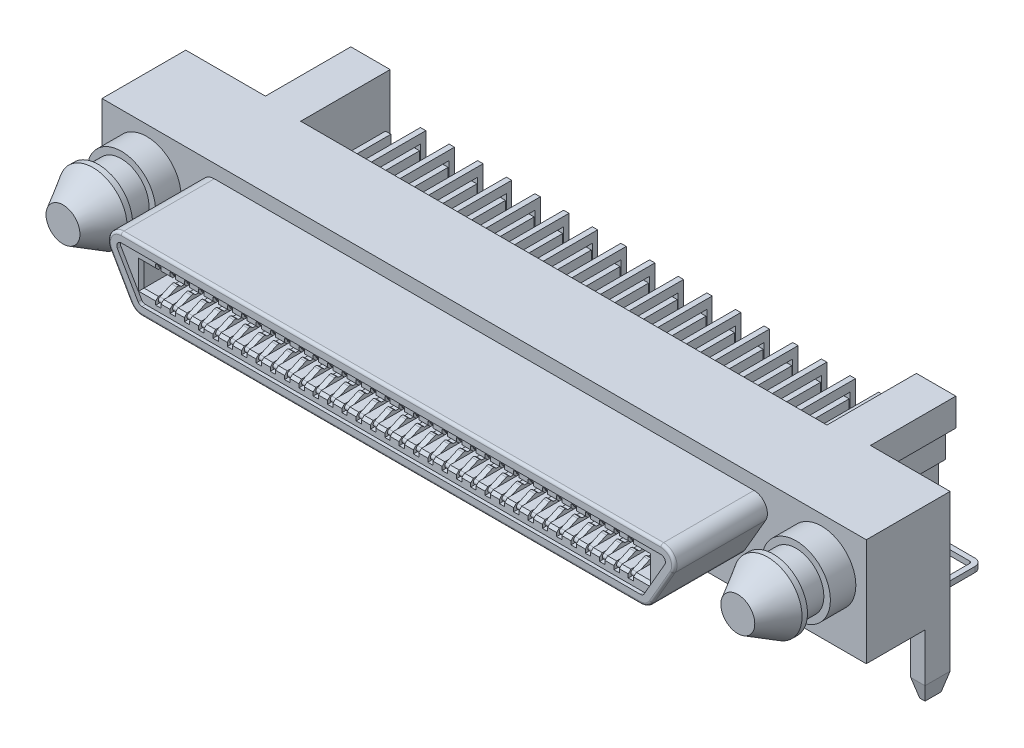
SolidWorks part; units mm, degrees
ref_plane "Front Plane" through (0, 0, 0) normal (0, 0, 1) x (1, 0, 0)
ref_plane "Top Plane" through (0, 0, 0) normal (0, 1, 0) x (1, 0, 0)
ref_plane "Right Plane" through (0, 0, 0) normal (1, 0, 0) x (0, 0, -1)
ref_plane "Pos 1 Plane" through (13.2, 0, 0) normal (1, 0, 0) x (0, 0, -1)
ref_plane "Pos 2 Plane" through (12.4, 0, 0) normal (1, 0, 0) x (0, 0, -1)
ref_plane "Weld Tab Plane" through (-16.175, 0, 0) normal (1, 0, 0) x (0, 0, -1)
ref_plane "Guide Post 1 Plane" through (-18.85, 0, 0) normal (1, 0, 0) x (0, 0, -1)
sketch "Sketch1" plane through (0, 0, 0) normal (0, 1, 0) x (1, 0, 0)
  line L0 (0, 0) -> (0, 18.3021) construction
  line L1 (16.9, 9.1) -> (16.9, 4.33)
  line L2 (-16.9, 9.1) -> (16.9, 9.1)
  line L3 (21.35, 4.33) -> (16.9, 4.33)
  line L5 (21.35, 4.33) -> (21.35, 0)
  line L6 (-21.35, 4.33) -> (-16.9, 4.33)
  line L7 (-16.9, 9.1) -> (-16.9, 4.33)
  line L8 (21.35, 0) -> (-21.35, 0)
  line L12 (-21.35, 0) -> (-21.35, 4.33)
  point P7 (0, 0)
  dimension "D1" = 4.33
  dimension "D2" = 4.45
  dimension "D3" = 42.7
  dimension "D5" = 9.1
extrude "Body 1" add sketch "Sketch1" along normal blind 6
sketch "Sketch68" plane through (0, 6, 0) normal (0, 1, 0) x (1, 0, 0)
  line L0 (16.9, 9.1) -> (-16.9, 9.1) construction
  line L1 (-14.7, 9.1) -> (14.7, 9.1)
  line L2 (-14.7, 9.1) -> (-14.7, 4.1)
  line L3 (-14.7, 4.1) -> (14.7, 4.1)
  line L4 (14.7, 9.1) -> (14.7, 4.1)
  line L5 (0, 0) -> (0, 13.0078) construction
  line L6 (-21.35, 0) -> (21.35, 0) construction
  line L7 (-14.7, 9.1) -> (14.7, 4.1) construction
  line L8 (-16.9, 9.1) -> (-16.9, 4.33) construction
  point P10 (0, 6.6)
  dimension "D1" = 5
  dimension "D2" = 2.2
extrude "Body 1 Cut 1" cut sketch "Sketch68" against normal blind 114.3
sketch "Sketch76" plane through (0, 0, 0) normal (0, 0, 1) x (1, 0, 0)
  line L0 (21.35, 6) -> (21.35, 0) construction
  line L1 (-21.35, 6) -> (21.35, 6)
  line L2 (-21.35, 6) -> (-21.35, 0)
  line L3 (-21.35, 0) -> (21.35, 0)
  line L4 (21.35, 6) -> (21.35, 0)
  line L9 (-21.35, 0) -> (21.35, 0) construction
  line L10 (-21.35, 6) -> (-21.35, 0) construction
  line L11 (-21.35, 6) -> (21.35, 6) construction
extrude "Body 3" add sketch "Sketch76" along normal blind 0.35
sketch "Sketch75" plane through (-18.85, 0, 0) normal (1, 0, 0) x (0, 0, -1)
  line L2 (4.33, 0) -> (-0.35, 0) construction
  line L3 (-0.35, 5.4125) -> (-1.772, 5.4125)
  line L4 (-0.35, 5.4125) -> (-0.35, 3.4975)
  line L5 (-0.35, 3.4975) -> (-5.03, 3.4975)
  line L6 (-5.03, 4.446) -> (-5.03, 3.4975)
  line L7 (-3.356, 5.4125) -> (-5.03, 4.446)
  line L8 (-3.052, 5.4125) -> (-3.052, 5.0475)
  line L9 (-1.772, 5.0475) -> (-3.052, 5.0475)
  line L10 (-1.772, 5.4125) -> (-1.772, 5.0475)
  line L11 (-3.052, 5.4125) -> (-3.356, 5.4125)
  line L12 (-0.35, 0) -> (-0.35, 6) construction
  line L15 (2.165, 3.4975) -> (-5.6325, 3.4975) construction
  dimension "D1" = 1.915
  dimension "D2" = 1.55
  dimension "D3" = 3.4975
  dimension "D4" = 120
  dimension "D5" = 1.422
  dimension "D6" = 1.28
  dimension "D7" = 4.68
  dimension "D8" = 0.304
revolve "Guide Post 1" add sketch "Sketch75" angle 360 about L15
mirror "Guide Post 1 Mir" about plane through (0, 0, 0) normal (1, 0, 0) of "Guide Post 1"
sketch "Sketch65" plane through (0, 0, -9.1) normal (0, 0, -1) x (-1, 0, 0)
  line L0 (0, 0) -> (0, 7.7991) construction
  line L1 (15.925, 4.45) -> (16.025, 4.45)
  line L2 (15.925, 4.45) -> (15.925, 0)
  line L4 (16.9, 4.45) -> (16.9, 0)
  line L5 (16.175, 4.8474) -> (16.175, -0.272) construction
  line L6 (16.175, 2.53) -> (16.175, -2.53) construction
  line L7 (16.325, 4.45) -> (16.9, 4.45)
  line L8 (16.025, 4.8474) -> (16.325, 4.8474)
  line L9 (16.025, 4.8474) -> (16.025, 4.45)
  line L10 (15.925, 0) -> (16.9, 0)
  line L11 (16.325, 4.8474) -> (16.325, 4.45)
  line L12 (-16.9, 0) -> (-14.7, 0) construction
  line L13 (16.9, 6) -> (16.9, 0) construction
  line L14 (14.7, 6) -> (16.9, 6) construction
  dimension "D1" = 1.1526
  dimension "D2" = 0.3974
  dimension "D3" = 0.15
  dimension "D4" = 0.15
  dimension "D5" = 0.1
extrude "WT Slot" cut sketch "Sketch65" against normal up to surface (4.77 mm away) up to face at (-19.125, 3, -4.33)
sketch "Sketch66" plane through (-16.175, 0, 0) normal (1, 0, 0) x (0, 0, -1)
  line L0 (4.33, 0) -> (9.1, 0) construction
  line L1 (9.1, 4.7474) -> (4.33, 4.7474)
  line L2 (9.1, 4.7474) -> (9.1, 2.6474)
  line L3 (9.1, 2.6474) -> (7.5, 2.6474)
  line L4 (4.33, 4.7474) -> (4.33, 2.6474)
  line L5 (-0.35, 0) -> (-0.35, 6) construction
  line L6 (6.25, 3.2861) -> (6.25, -2.236) construction
  line L8 (7.5, 2.6474) -> (7.5, 0.3)
  line L9 (7.5, 0.3) -> (7.2084, 0.3)
  line L10 (5, 2.6474) -> (5, 0.3)
  line L11 (5.2916, 1.4737) -> (5.2916, 0.3)
  line L13 (6.05, 1.4737) -> (6.05, -2.28)
  line L14 (5.6916, 1.4737) -> (5.6916, -1.5871)
  line L15 (7.0084, 1.4737) -> (5.4916, 1.4737) construction
  line L16 (5.5825, -1.9404) -> (5.7632, -2.3416)
  line L17 (5.6714, -1.6624) -> (5.5895, -1.8036)
  line L18 (7.2084, 1.4737) -> (7.2084, 0.3)
  line L19 (6.8286, -1.6624) -> (6.9105, -1.8036)
  line L20 (6.9175, -1.9404) -> (6.7368, -2.3416)
  line L21 (6.45, 1.4737) -> (6.45, -2.28)
  line L22 (6.8084, 1.4737) -> (6.8084, -1.5871)
  line L23 (5.2916, 0.3) -> (5, 0.3)
  line L24 (5, 2.6474) -> (4.33, 2.6474)
  arc A0 (6.45, 1.4737) -> (6.05, 1.4737) centre (6.25, 1.4737) ccw
  arc A1 (7.2084, 1.4737) -> (6.8084, 1.4737) centre (7.0084, 1.4737) ccw
  arc A2 (5.6916, 1.4737) -> (5.2916, 1.4737) centre (5.4916, 1.4737) ccw
  arc A3 (5.7632, -2.3416) -> (6.05, -2.28) centre (5.9, -2.28) ccw
  arc A4 (5.5895, -1.8036) -> (5.5825, -1.9404) centre (5.7193, -1.8788) ccw
  arc A5 (5.6714, -1.6624) -> (5.6916, -1.5871) centre (5.5416, -1.5871) ccw
  arc A6 (6.8286, -1.6624) -> (6.8084, -1.5871) centre (6.9584, -1.5871) cw
  arc A7 (6.9105, -1.8036) -> (6.9175, -1.9404) centre (6.7807, -1.8788) cw
  arc A8 (6.7368, -2.3416) -> (6.45, -2.28) centre (6.6, -2.28) cw
  point P4 (6.25, 1.6737)
  dimension "D5" = 0.3
  dimension "D6" = 2.43
  dimension "D7" = 0.15
  dimension "D10" = 0.2917
  dimension "D11" = 1.1737
  dimension "D8" = 0.1807
  dimension "D2" = 0.2
  dimension "D9" = 0.4012
  dimension "D3" = 1.25
  dimension "D4" = 0.2916
  dimension "D12" = 1.92
  dimension "D13" = 2.85
  dimension "D14" = 1.1737
  dimension "D15" = 0.2916
  dimension "D16" = 2.1
  dimension "D17" = 6.6
extrude "WT 1" add sketch "Sketch66" along normal blind 0.15 and the other way blind 0.15
sketch "Sketch67" plane through (0, 0, 0) normal (0, 1, 0) x (1, 0, 0)
  line L0 (0, 0) -> (0, 12.3648) construction
  line L1 (-19.5749, 7.5) -> (-16.025, 7.5)
  line L2 (-19.9749, 7.1) -> (-19.9749, 5.4)
  line L3 (-19.5749, 5) -> (-16.025, 5)
  line L4 (-16.025, 7.5) -> (-16.025, 7.2084)
  line L5 (-16.325, 7.5) -> (-16.025, 7.5) construction
  line L6 (-16.325, 5) -> (-16.025, 5) construction
  line L7 (-19.5749, 7.2084) -> (-16.025, 7.2084)
  line L8 (-19.5749, 7.2084) -> (-16.3166, 7.2084) construction
  line L9 (-19.5749, 5.2916) -> (-16.025, 5.2916)
  line L10 (-19.6833, 7.1) -> (-19.6833, 5.4)
  line L11 (-16.3166, 7.2084) -> (-16.3166, 5.2916) construction
  line L12 (-19.5749, 5.2916) -> (-16.3166, 5.2916) construction
  line L13 (-16.025, 5.2916) -> (-16.025, 5)
  line L14 (-16.025, 7.5) -> (-16.025, 5) construction
  line L15 (-16.025, 7.2084) -> (-16.025, 7.5) construction
  line L19 (-16.325, 5.2916) -> (-16.025, 5.2916) construction
  arc A0 (-19.5749, 7.5) -> (-19.9749, 7.1) centre (-19.5749, 7.1) ccw
  arc A1 (-19.5749, 5) -> (-19.9749, 5.4) centre (-19.5749, 5.4) cw
  arc A2 (-19.5749, 5.2916) -> (-19.6833, 5.4) centre (-19.5749, 5.4) cw
  arc A3 (-19.5749, 7.2084) -> (-19.6833, 7.1) centre (-19.5749, 7.1) ccw
  dimension "D2" = 0.4
  dimension "D1" = 3.9499
extrude "WT 2" add sketch "Sketch67" along normal blind 0.3
mirror "WT Slot Mir" about plane through (0, 0, 0) normal (1, 0, 0) of "WT 2", "WT 1", "WT Slot"
sketch "Sketch61" plane through (0, 0, 0.35) normal (0, 0, 1) x (1, 0, 0)
  line L0 (0, 0) -> (0, 9.2865) construction
  line L1 (-15.075, 5.25) -> (15.075, 5.25)
  line L2 (14.5698, 2.125) -> (15.7245, 4.125)
  line L3 (-13.9203, 1.75) -> (13.9203, 1.75)
  line L4 (0, 3.5) -> (6.9442, 3.5) construction
  line L5 (-15.7245, 4.125) -> (-14.5698, 2.125)
  line L6 (-15.075, 4.75) -> (15.075, 4.75)
  line L7 (14.1368, 2.375) -> (15.2915, 4.375)
  line L8 (-13.9203, 2.25) -> (13.9203, 2.25)
  line L9 (-15.2915, 4.375) -> (-14.1368, 2.375)
  line L13 (-21.35, 0) -> (21.35, 0) construction
  arc A0 (-15.075, 5.25) -> (-15.7245, 4.125) centre (-15.075, 4.5) ccw
  arc A1 (-13.9203, 1.75) -> (-14.5698, 2.125) centre (-13.9203, 2.5) cw
  arc A2 (13.9203, 1.75) -> (14.5698, 2.125) centre (13.9203, 2.5) ccw
  arc A3 (15.075, 5.25) -> (15.7245, 4.125) centre (15.075, 4.5) cw
  arc A4 (15.075, 4.75) -> (15.2915, 4.375) centre (15.075, 4.5) cw
  arc A5 (13.9203, 2.25) -> (14.1368, 2.375) centre (13.9203, 2.5) ccw
  arc A6 (-13.9203, 2.25) -> (-14.1368, 2.375) centre (-13.9203, 2.5) cw
  arc A7 (-15.075, 4.75) -> (-15.2915, 4.375) centre (-15.075, 4.5) ccw
  point P7 (0, 1.75)
  dimension "D4" = 0.75
  dimension "D5" = 0.75
  dimension "D1" = 1.75
  dimension "D6" = 31.65
  dimension "D2" = 3.5
  dimension "D3" = 60
  dimension "D8" = 3.5
  dimension "D7" = 0.5
extrude "Body 2" add sketch "Sketch61" along normal blind 5.2
fillet "Body 2 Fil" radius 0.15 8 edges at (15.7245, 4.875, 5.55) (15.1472, 3.125, 5.55) (14.2953, 1.8505, 5.55) (0, 1.75, 5.55) (-14.2953, 1.8505, 5.55) (-15.1472, 3.125, 5.55) (-15.7245, 4.875, 5.55) (0, 5.25, 5.55)
sketch "Sketch62" plane through (0, 0, 0.35) normal (0, 0, 1) x (1, 0, 0)
  line L0 (0, 0) -> (0, 8.2343) construction
  line L1 (-14.15, 4.15) -> (14.15, 4.15)
  line L2 (-14.15, 4.15) -> (-14.15, 2.85)
  line L3 (-14.15, 2.85) -> (14.15, 2.85)
  line L4 (15.075, 4.75) -> (-15.075, 4.75)
  line L5 (14.1368, 2.375) -> (15.2915, 4.375)
  line L6 (-13.9203, 2.25) -> (13.9203, 2.25)
  line L7 (-15.2915, 4.375) -> (-14.1368, 2.375)
  line L8 (15.075, 4.75) -> (-15.075, 4.75)
  line L9 (14.1368, 2.375) -> (15.2915, 4.375)
  line L10 (-13.9203, 2.25) -> (13.9203, 2.25)
  line L11 (-15.2915, 4.375) -> (-14.1368, 2.375)
  line L12 (14.15, 4.15) -> (14.15, 2.85)
  line L13 (-14.15, 3.5) -> (14.15, 3.5) construction
  line L15 (-21.35, 0) -> (21.35, 0) construction
  arc A4 (15.2915, 4.375) -> (15.075, 4.75) centre (15.075, 4.5) ccw
  arc A5 (13.9203, 2.25) -> (14.1368, 2.375) centre (13.9203, 2.5) ccw
  arc A6 (-14.1368, 2.375) -> (-13.9203, 2.25) centre (-13.9203, 2.5) ccw
  arc A7 (-15.075, 4.75) -> (-15.2915, 4.375) centre (-15.075, 4.5) ccw
  arc A8 (15.2915, 4.375) -> (15.075, 4.75) centre (15.075, 4.5) ccw
  arc A9 (13.9203, 2.25) -> (14.1368, 2.375) centre (13.9203, 2.5) ccw
  arc A10 (-14.1368, 2.375) -> (-13.9203, 2.25) centre (-13.9203, 2.5) ccw
  arc A11 (-15.075, 4.75) -> (-15.2915, 4.375) centre (-15.075, 4.5) ccw
  point P18 (0, 2.85)
  dimension "D2" = 0.925
  dimension "D3" = 1.3
  dimension "D4" = 3.5
  dimension "D1" = 0
extrude "Core 1" add sketch "Sketch62" along normal blind 5
chamfer "Core Lead-in" distance 0.15 angle 45 4 edges at (14.15, 3.5, 5.35) (0, 2.85, 5.35) (-14.15, 3.5, 5.35) (0, 4.15, 5.35)
sketch "Sketch70" plane through (0, 0, 0) normal (0, -1, 0) x (1, 0, 0)
  line L0 (21.35, -3.63) -> (20.55, -3.63) construction
  line L1 (21.35, -2.93) -> (20.55, -2.93)
  line L2 (21.35, -2.93) -> (21.35, -4.33)
  line L3 (21.35, -4.33) -> (20.55, -4.33)
  line L4 (20.55, -2.93) -> (20.55, -4.33)
  line L5 (21.35, -4.33) -> (15.925, -4.33) construction
  line L6 (0, 0) -> (0, -5.5321) construction
  line L7 (-20.55, -2.93) -> (-20.55, -4.33)
  line L8 (-21.35, -4.33) -> (-20.55, -4.33)
  line L9 (-21.35, -2.93) -> (-21.35, -4.33)
  line L10 (-21.35, -2.93) -> (-20.55, -2.93)
  line L11 (20.95, -2.93) -> (20.95, -4.33) construction
  line L14 (21.35, 0.35) -> (21.35, -4.33) construction
  dimension "D1" = 0.8
  dimension "D2" = 1.4
extrude "Guide Post 2" add sketch "Sketch70" along normal blind 3.7
chamfer "Guide Post 2  Point" distance 1 distance2 0.25 8 edges at (20.95, -3.7, -4.33) (21.35, -3.7, -3.63) (20.95, -3.7, -2.93) (20.55, -3.7, -3.63) (-20.55, -3.7, -3.63) (-20.95, -3.7, -4.33) (-21.35, -3.7, -3.63) (-20.95, -3.7, -2.93) first distance on face at (18.0385, 2.1537, -4.33) first distance on face at (21.35, 0.4583, -2.03) first distance on face at (21.05, -2.3125, -2.93) first distance on face at (20.55, -2.3125, -3.455) first distance on face at (-20.55, -1.85, -3.63) first distance on face at (-17.8458, 2.3079, -4.33) first distance on face at (-21.35, 0.7667, -2.3033) first distance on face at (-20.95, -1.85, -2.93)
sketch "Sketch63" plane through (13.2, 0, 0) normal (1, 0, 0) x (0, 0, -1)
  line L0 (-5.35, 4.375) -> (-5.35, 2.375) construction
  line L1 (-0.35, 4.5) -> (-5.35, 4.5)
  line L2 (-0.35, 4.5) -> (-0.35, 4)
  line L3 (-0.35, 4) -> (-5.35, 4)
  line L4 (-5.35, 4.5) -> (-5.35, 4)
  line L6 (-5.4, 5.25) -> (-0.35, 5.25) construction
  line L7 (-5.2, 3.5) -> (-6.5045, 3.5) construction
  line L8 (-5.2, 4.15) -> (-5.2, 2.85) construction
  line L9 (-5.35, 2.5) -> (-5.35, 3)
  line L10 (-0.35, 3) -> (-5.35, 3)
  line L11 (-0.35, 2.5) -> (-0.35, 3)
  line L12 (-0.35, 2.5) -> (-5.35, 2.5)
  line L13 (-0.35, 0) -> (-0.35, 6) construction
  dimension "D1" = 0.75
  dimension "D2" = 0.5
extrude "Slot" cut sketch "Sketch63" against normal blind 0.15 and the other way blind 0.15
pattern_linear "Slot Pat" count 34 spacing 0.8 along (-1, 0, 0) of "Slot"
sketch "Sketch69" plane through (13.2, 0, 0) normal (1, 0, 0) x (0, 0, -1)
  line L0 (-0.35, 4.5) -> (-5.35, 4.5) construction
  line L1 (-5.05, 4.5) -> (8.64, 4.5)
  line L2 (-5.2, 3.5) -> (-5.693, 3.5) construction
  line L3 (-4.2309, 4) -> (8.34, 4)
  line L4 (3.63, -2.7) -> (3.63, 0) construction
  line L5 (2.93, -2.7) -> (4.33, -2.7) construction
  line L8 (-5.1125, 4.2136) -> (-4.4636, 3.9164)
  line L12 (6.14, 2.0929) -> (6.14, -4.4763) construction
  line L14 (-4.3045, 3.938) -> (-4.2309, 4)
  line L15 (-5.2, 2.85) -> (-5.2, 4.15) construction
  line L16 (-5.05, 2.5) -> (5.99, 2.5)
  line L17 (-4.2309, 3) -> (6.29, 3)
  line L18 (-4.3045, 3.062) -> (-4.2309, 3)
  line L19 (-5.1125, 2.7864) -> (-4.4636, 3.0836)
  line L22 (5.99, 1.7) -> (6.29, 1.7)
  line L23 (8.64, 4.5) -> (8.64, 1.7)
  line L24 (8.34, 1.7) -> (8.34, 4)
  line L25 (5.99, 2.5) -> (5.99, 1.7)
  line L27 (-5.35, 2.5) -> (-0.35, 2.5) construction
  line L29 (8.49, -4.4763) -> (8.49, 2.39) construction
  line L30 (-5.55, 2.2) -> (-5.55, 4.2) construction
  line L31 (6.29, 1.7) -> (6.29, 3)
  line L32 (8.64, 1.7) -> (8.34, 1.7)
  line L33 (4.33, 0) -> (9.1, 0) construction
  arc A0 (-5.05, 4.5) -> (-5.1125, 4.2136) centre (-5.05, 4.35) ccw
  arc A1 (-4.3045, 3.938) -> (-4.4636, 3.9164) centre (-4.4011, 4.0528) cw
  arc A2 (-4.3045, 3.062) -> (-4.4636, 3.0836) centre (-4.4011, 2.9472) ccw
  arc A3 (-5.05, 2.5) -> (-5.1125, 2.7864) centre (-5.05, 2.65) cw
  dimension "D7" = 0.15
  dimension "D8" = 0.15
  dimension "D10" = 0.7137
  dimension "D11" = 0.4472
  dimension "D1" = 0.5
  dimension "D2" = 0.15
  dimension "D3" = 2.51
  dimension "D4" = 0.3
  dimension "D5" = 0.15
  dimension "D6" = 2.35
  dimension "D9" = 0.3
  dimension "D12" = 220.101
  dimension "D13" = 0.5
  dimension "D14" = 1.7
extrude "Contact 1" add sketch "Sketch69" along normal blind 0.15 and the other way blind 0.15
sketch "Sketch73" plane through (12.4, 0, 0) normal (1, 0, 0) x (0, 0, -1)
  line L0 (4.84, 1.7) -> (4.84, 2.5)
  line L1 (4.99, 1.7) -> (4.99, 2.8466) construction
  line L2 (7.34, 1.7) -> (7.34, 4.2866) construction
  line L3 (3.63, -2.7) -> (3.63, -4.0265) construction
  line L4 (2.93, -2.7) -> (4.33, -2.7) construction
  line L9 (8.64, 4.5) -> (-5.05, 4.5)
  line L10 (8.64, 1.7) -> (8.64, 4.5)
  line L11 (7.49, 1.7) -> (7.49, 4.5)
  line L12 (8.34, 1.7) -> (8.64, 1.7)
  line L13 (7.19, 1.7) -> (7.49, 1.7)
  line L14 (8.34, 4) -> (8.34, 1.7)
  line L15 (-4.2309, 4) -> (8.34, 4)
  line L16 (-4.3045, 3.938) -> (-4.2309, 4)
  line L17 (-5.1125, 4.2136) -> (-4.4636, 3.9164)
  line L18 (7.49, 4.5) -> (-5.05, 4.5)
  line L19 (7.19, 4) -> (7.19, 1.7)
  line L20 (5.99, 1.7) -> (6.29, 1.7)
  line L21 (4.84, 1.7) -> (5.14, 1.7)
  line L22 (6.29, 1.7) -> (6.29, 3)
  line L23 (5.14, 1.7) -> (5.14, 3)
  line L24 (-4.2309, 4) -> (7.19, 4)
  line L25 (-4.3045, 3.938) -> (-4.2309, 4)
  line L26 (-5.1125, 4.2136) -> (-4.4636, 3.9164)
  line L27 (-5.05, 2.5) -> (5.99, 2.5)
  line L28 (-4.4636, 3.0836) -> (-5.1125, 2.7864)
  line L29 (-4.2309, 3) -> (-4.3045, 3.062)
  line L30 (6.29, 3) -> (-4.2309, 3)
  line L35 (5.99, 2.5) -> (5.99, 1.7)
  line L36 (-5.05, 2.5) -> (4.84, 2.5)
  line L37 (-4.4636, 3.0836) -> (-5.1125, 2.7864)
  line L38 (-4.2309, 3) -> (-4.3045, 3.062)
  line L39 (5.14, 3) -> (-4.2309, 3)
  arc A2 (-4.4636, 3.9164) -> (-4.3045, 3.938) centre (-4.4011, 4.0528) ccw
  arc A3 (-5.05, 4.5) -> (-5.1125, 4.2136) centre (-5.05, 4.35) ccw
  arc A4 (-4.4636, 3.9164) -> (-4.3045, 3.938) centre (-4.4011, 4.0528) ccw
  arc A5 (-5.05, 4.5) -> (-5.1125, 4.2136) centre (-5.05, 4.35) ccw
  arc A6 (-5.1125, 2.7864) -> (-5.05, 2.5) centre (-5.05, 2.65) ccw
  arc A7 (-4.3045, 3.062) -> (-4.4636, 3.0836) centre (-4.4011, 2.9472) ccw
  arc A8 (-5.1125, 2.7864) -> (-5.05, 2.5) centre (-5.05, 2.65) ccw
  arc A9 (-4.3045, 3.062) -> (-4.4636, 3.0836) centre (-4.4011, 2.9472) ccw
  dimension "D3" = 0.3
  dimension "D4" = 1.36
  dimension "D5" = 2.35
  dimension "D1" = 0
  dimension "D2" = 0
extrude "Contact 2" add sketch "Sketch73" along normal blind 0.15 and the other way blind 0.15
pattern_linear "Contact 1 Pat" count 17 spacing 1.6 along (-1, 0, 0) of "Contact 1"
pattern_linear "Contact 2 Pat" count 17 spacing 1.6 along (-1, 0, 0) of "Contact 2"
sketch "Sketch77" plane through (0, 1.7, 0) normal (0, -1, 0) x (1, 0, 0)
  line L1 (12.85, -8.64) -> (13.15, -8.64)
  line L2 (12.85, -8.64) -> (12.85, -8.34)
  line L3 (12.85, -8.34) -> (13.15, -8.34)
  line L4 (13.15, -8.64) -> (13.15, -8.34)
  line L5 (13.55, -6.29) -> (13.25, -6.29)
  line L6 (13.55, -6.29) -> (13.55, -5.99)
  line L7 (13.55, -5.99) -> (13.25, -5.99)
  line L8 (13.25, -6.29) -> (13.25, -5.99)
  line L9 (13.05, -6.29) -> (13.35, -6.29) construction
  line L10 (13.05, -8.64) -> (13.35, -8.64) construction
  line L12 (13.35, -5.99) -> (13.35, -6.29) construction
  line L13 (13.05, -8.34) -> (13.05, -8.64) construction
  dimension "D1" = 0.3
  dimension "D2" = 0.3
  dimension "D3" = 0.1
  dimension "D4" = 0.1
extrude "Contact1 Tail" add sketch "Sketch77" along normal blind 3.99
sketch "Sketch78" plane through (0, 1.7, 0) normal (0, -1, 0) x (1, 0, 0)
  line L0 (12.25, -4.84) -> (12.55, -4.84) construction
  line L1 (12.75, -4.84) -> (12.45, -4.84)
  line L2 (12.75, -4.84) -> (12.75, -5.14)
  line L3 (12.75, -5.14) -> (12.45, -5.14)
  line L4 (12.45, -4.84) -> (12.45, -5.14)
  line L5 (12.25, -7.49) -> (12.55, -7.49) construction
  line L6 (12.05, -7.49) -> (12.35, -7.49)
  line L7 (12.05, -7.49) -> (12.05, -7.19)
  line L8 (12.05, -7.19) -> (12.35, -7.19)
  line L9 (12.35, -7.49) -> (12.35, -7.19)
  line L12 (12.55, -4.84) -> (12.55, -5.14) construction
  line L13 (12.25, -7.19) -> (12.25, -7.49) construction
  dimension "D1" = 0.3
  dimension "D2" = 0.1
  dimension "D3" = 0.1
extrude "Contact3 Tail" add sketch "Sketch78" along normal blind 3.99
pattern_linear "Contact1 Tail Pattern" count 17 spacing 1.6 along (-1, 0, 0) of "Contact1 Tail"
pattern_linear "Contact3 Tail Pattern" count 17 spacing 1.6 along (1, 0, 0) of "Contact3 Tail"
